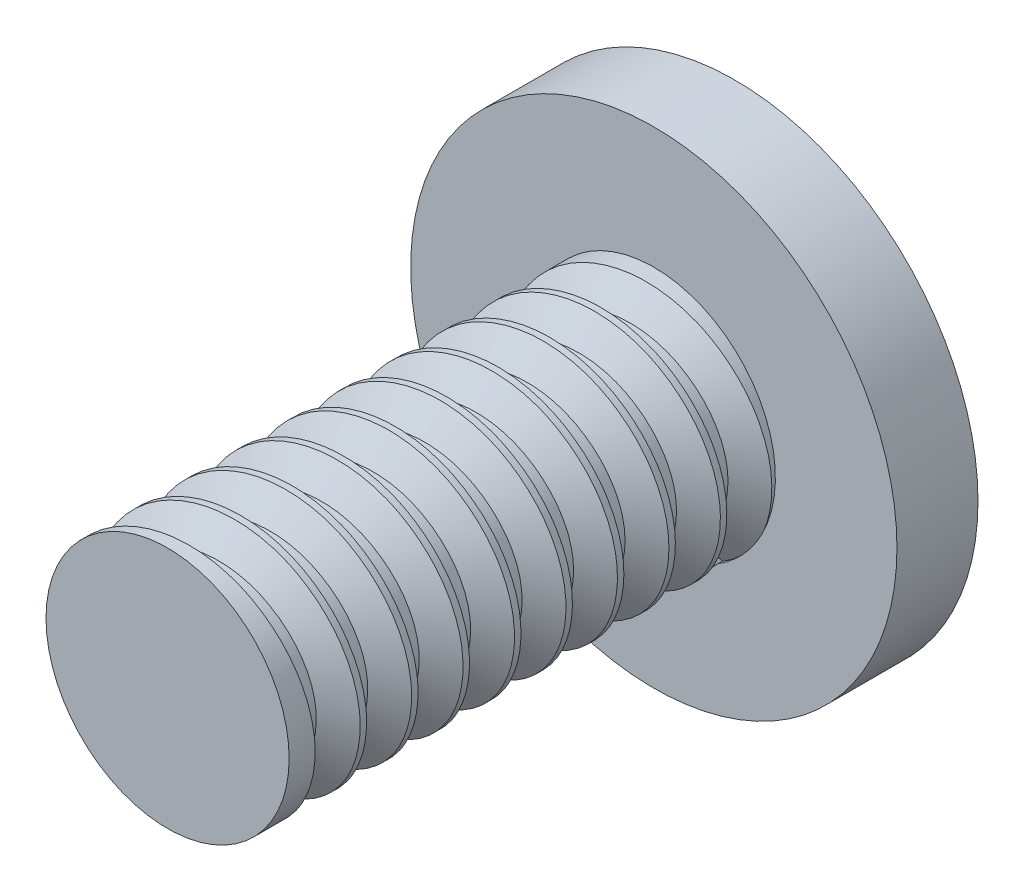
SolidWorks part; units mm, degrees
ref_plane "前视基准面" through (0, 0, 0) normal (0, 0, 1) x (1, 0, 0)
ref_plane "上视基准面" through (0, 0, 0) normal (0, 1, 0) x (1, 0, 0)
ref_plane "右视基准面" through (0, 0, 0) normal (1, 0, 0) x (0, 0, -1)
sketch "草图1" plane through (0, 0, 0) normal (0, 0, 1) x (1, 0, 0)
  circle A0 centre (0, 0) radius 3
  dimension "D1" = 6
extrude "凸台-拉伸1" add sketch "草图1" along normal blind 1
sketch "草图2" plane through (0, 0, 1) normal (0, 0, 1) x (1, 0, 0)
  circle A0 centre (0, 0) radius 1.5
  dimension "D1" = 3
extrude "凸台-拉伸2" add sketch "草图2" along normal blind 6
thread "螺纹线1" pitch 0.635 method cut profile "螺纹线轮廓1" start angle 0, offset 0, length 5.5, pitch 0.635, diameter 3
ref_plane "基准面4" through (-1.5, 0, 7) normal (0, -1, 0) x (-1, 0, 0)
sketch "螺纹线轮廓1" plane through (-1.5, 0, 7) normal (0, -1, 0) x (-1, 0, 0)
  line L0 (0, 0) -> (0, 0.635) construction
  line L11 (0, 0) -> (0, 0.5556)
  line L12 (0, 0.5556) -> (-0.3437, 0.3572)
  line L13 (-0.3437, 0.3572) -> (-0.3437, 0.1984)
  line L15 (-0.3437, 0.1984) -> (0, 0)
  line L17 (-0.3437, 0.2778) -> (0, 0.2778) construction
  point P2 (0, 0)
  dimension "Pitch" = 0.635
  dimension "Profile_Angle" = 60
  dimension "Profile_Land" = 0.1588
  dimension "Profile_Height" = 0.3437
sketch "草图6" plane through (0, 0, 0) normal (0, 0, -1) x (-1, 0, 0)
  line L1 (1.5433, -0.7863) -> (1.4526, 0.9434)
  line L2 (1.4526, 0.9434) -> (-0.0907, 1.7297)
  line L3 (-0.0907, 1.7297) -> (-1.5433, 0.7863)
  line L4 (-1.5433, 0.7863) -> (-1.4526, -0.9434)
  line L5 (-1.4526, -0.9434) -> (0.0907, -1.7297)
  line L6 (0.0907, -1.7297) -> (1.5433, -0.7863)
  circle A0 centre (0, 0) radius 1.5 construction
  dimension "D1" = 3
extrude "切除-拉伸1" cut sketch "草图6" against normal blind 0.5
